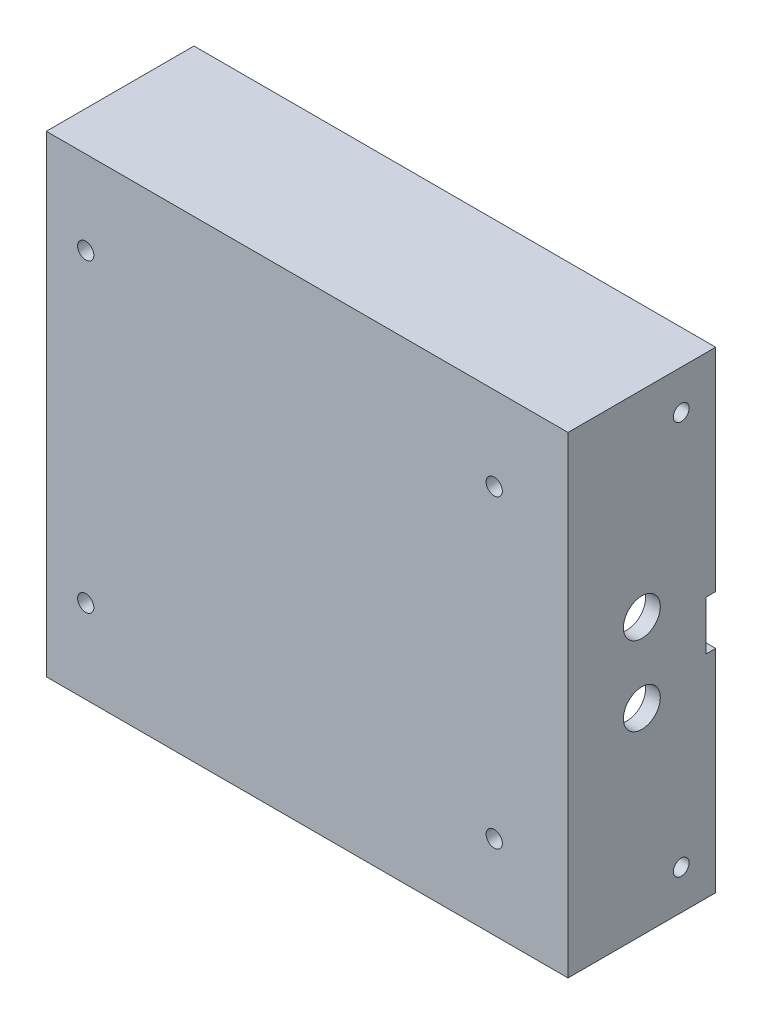
SolidWorks part; units mm, degrees
ref_plane "Front Plane" through (0, 0, 0) normal (0, 0, 1) x (1, 0, 0)
ref_plane "Top Plane" through (0, 0, 0) normal (0, 1, 0) x (1, 0, 0)
ref_plane "Right Plane" through (0, 0, 0) normal (1, 0, 0) x (0, 0, -1)
sketch "Sketch1" plane through (0, 0, 0) normal (0, 0, 1) x (1, 0, 0)
  line L1 (-50, -45) -> (50, -45)
  line L2 (-50, -45) -> (-50, 45)
  line L3 (-50, 45) -> (50, 45)
  line L4 (50, -45) -> (50, 45)
  line L5 (-50, -45) -> (50, 45) construction
  line L6 (-50, 45) -> (50, -45) construction
  line L7 (-45, -31) -> (38, -31)
  line L8 (-45, -31) -> (-45, 31)
  line L9 (-45, 31) -> (38, 31)
  line L10 (38, -31) -> (38, 31)
  line L11 (-45, -31) -> (38, 31) construction
  line L12 (-45, 31) -> (38, -31) construction
  circle A0 centre (-45, 31) radius 1.65
  circle A1 centre (38, 31) radius 1.65
  circle A2 centre (38, -31) radius 1.65
  circle A3 centre (-45, -31) radius 1.65
  point P0 (0, 0)
  point P6 (-3.5, 0)
  dimension "D7" = 3.3
  dimension "D1" = 90
  dimension "D2" = 100
  dimension "D3" = 62
  dimension "D4" = 83
  dimension "D5" = 14
  dimension "D6" = 5
extrude "Boss-Extrude2" add sketch "Sketch1" along normal blind 3 contours L1 L4 L3 L2 A3 L8 A0 L9 A1 L10 A2 L7 | A3 L7 A2 L10 A1 L9 A0 L8 region at (-48.6546, 0, 0) region at (-3.5, 0, 0)
sketch "Sketch2" plane through (0, 0, 3) normal (0, 0, 1) x (1, 0, 0)
  line L1 (50, -45) -> (-50, -45)
  line L2 (50, -45) -> (50, 45)
  line L3 (50, 45) -> (-50, 45)
  line L4 (-50, -45) -> (-50, 45)
  line L5 (50, -45) -> (-50, 45) construction
  line L6 (50, 45) -> (-50, -45) construction
  line L7 (53, -48) -> (-53, -48)
  line L8 (53, -48) -> (53, 48)
  line L9 (53, 48) -> (-53, 48)
  line L10 (-53, -48) -> (-53, 48)
  line L11 (53, -48) -> (-53, 48) construction
  line L12 (53, 48) -> (-53, -48) construction
  point P0 (0, 0)
  point P7 (0, 0)
  dimension "D1" = 3
  dimension "D2" = 3
extrude "Boss-Extrude3" add sketch "Sketch2" against normal blind 30
sketch "Sketch3" plane through (-53, 0, 0) normal (-1, 0, 0) x (0, 0, 1)
  line L0 (-27, 48) -> (-27, -48) construction
  line L1 (-27, 48) -> (3, 48) construction
  line L2 (-27, -48) -> (3, -48) construction
  circle A0 centre (-20, -40) radius 1.6
  circle A1 centre (-20, 40) radius 1.6
  dimension "D1" = 3.2
  dimension "D2" = 7
  dimension "D3" = 8
  dimension "D4" = 8
  dimension "D5" = 7
  dimension "D6" = 3.2
extrude "Cut-Extrude1" cut sketch "Sketch3" against normal up to surface (106 mm away) up to face at (53, 0, -12)
sketch "Sketch4" plane through (53, 0, 0) normal (1, 0, 0) x (0, 0, -1)
  line L0 (27, -48) -> (27, 48) construction
  line L1 (27, 5) -> (25, 5)
  line L2 (27, 5) -> (27, -5)
  line L3 (27, -5) -> (25, -5)
  line L4 (25, 5) -> (25, -5)
  line L5 (27, -48) -> (-3, -48) construction
  line L6 (27, 48) -> (-3, 48) construction
  line L7 (-3, -48) -> (-3, 48) construction
  circle A0 centre (12, -8) radius 3.75
  circle A1 centre (12, 8) radius 3.75
  dimension "D4" = 7.5
  dimension "D5" = 7.5
  dimension "D6" = 15
  dimension "D7" = 40
  dimension "D8" = 40
  dimension "D9" = 15
  dimension "D1" = 2
  dimension "D2" = 10
  dimension "D3" = 43
extrude "Cut-Extrude3" cut sketch "Sketch4" against normal blind 10
